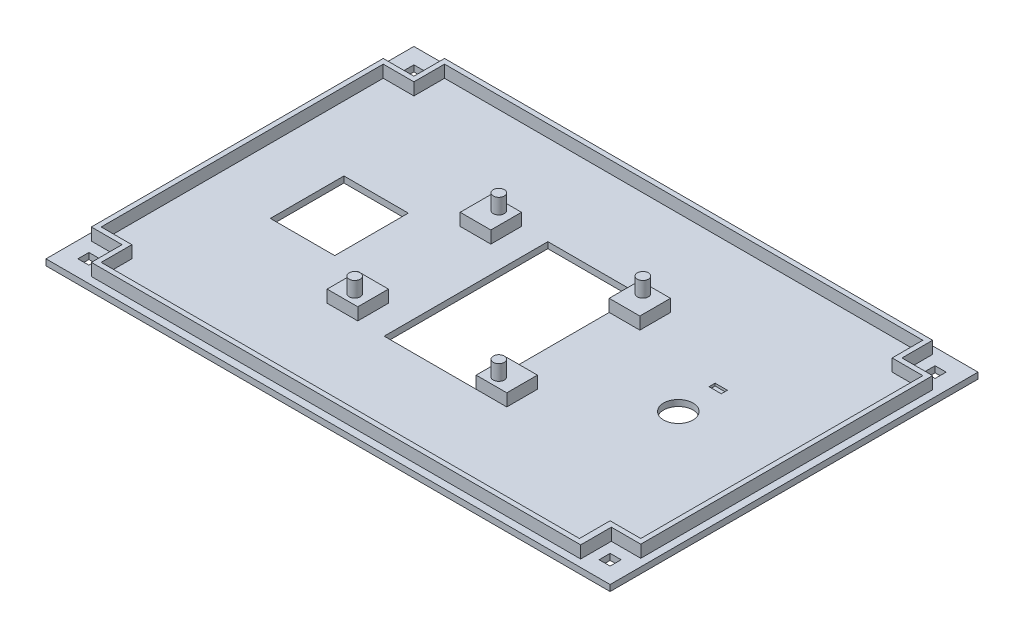
SolidWorks part; units mm, degrees
ref_plane "Спереди" through (0, 0, 0) normal (0, 0, 1) x (1, 0, 0)
ref_plane "Сверху" through (0, 0, 0) normal (0, 1, 0) x (1, 0, 0)
ref_plane "Справа" through (0, 0, 0) normal (1, 0, 0) x (0, 0, -1)
sketch "Эскиз1" plane through (0, 0, 0) normal (0, 1, 0) x (1, 0, 0)
  line L0 (0, 0) -> (92, 0)
  line L1 (0, 0) -> (0, 60)
  line L2 (0, 60) -> (92, 60)
  line L3 (92, 0) -> (92, 60)
  dimension "D1" = 60
  dimension "D2" = 92
extrude "Бобышка-Вытянуть1" add sketch "Эскиз1" along normal blind 1
sketch "Эскиз2" plane through (0, 1, 0) normal (0, 1, 0) x (1, 0, 0)
  line L0 (0, 60) -> (0, 0) construction
  line L1 (91, 1) -> (1, 1)
  line L2 (91, 1) -> (91, 59)
  line L3 (91, 59) -> (1, 59)
  line L4 (1, 1) -> (1, 59)
  line L5 (92, 60) -> (0, 60) construction
  line L6 (92, 0) -> (92, 60) construction
  line L7 (0, 0) -> (92, 0) construction
  line L8 (3.5, 4.4) -> (3.5, 2.6) construction
  line L9 (1, 59) -> (6, 59)
  line L10 (1, 59) -> (1, 54)
  line L11 (1, 54) -> (6, 54)
  line L12 (6, 59) -> (6, 54)
  line L13 (91, 59) -> (86, 59)
  line L14 (91, 59) -> (91, 54)
  line L15 (91, 54) -> (86, 54)
  line L16 (86, 59) -> (86, 54)
  line L17 (91, 1) -> (86, 1)
  line L18 (91, 1) -> (91, 6)
  line L19 (91, 6) -> (86, 6)
  line L20 (86, 1) -> (86, 6)
  line L21 (1, 1) -> (6, 1)
  line L22 (1, 1) -> (1, 6)
  line L23 (1, 6) -> (6, 6)
  line L24 (6, 1) -> (6, 6)
  line L25 (2.6, 57.4) -> (4.4, 57.4)
  line L26 (2.6, 57.4) -> (2.6, 55.6)
  line L27 (2.6, 55.6) -> (4.4, 55.6)
  line L28 (4.4, 57.4) -> (4.4, 55.6)
  line L29 (87.6, 57.4) -> (89.4, 57.4)
  line L30 (87.6, 57.4) -> (87.6, 55.6)
  line L31 (87.6, 55.6) -> (89.4, 55.6)
  line L32 (89.4, 57.4) -> (89.4, 55.6)
  line L33 (87.6, 4.4) -> (89.4, 4.4)
  line L34 (87.6, 4.4) -> (87.6, 2.6)
  line L35 (87.6, 2.6) -> (89.4, 2.6)
  line L36 (89.4, 4.4) -> (89.4, 2.6)
  line L37 (2.6, 4.4) -> (4.4, 4.4)
  line L38 (2.6, 4.4) -> (2.6, 2.6)
  line L39 (2.6, 2.6) -> (4.4, 2.6)
  line L40 (4.4, 4.4) -> (4.4, 2.6)
  line L41 (2.6, 3.5) -> (4.4, 3.5) construction
  line L42 (3.5, 57.4) -> (3.5, 55.6) construction
  line L43 (2.6, 56.5) -> (4.4, 56.5) construction
  line L44 (88.5, 57.4) -> (88.5, 55.6) construction
  line L45 (87.6, 56.5) -> (89.4, 56.5) construction
  line L46 (88.5, 4.4) -> (88.5, 2.6) construction
  line L47 (87.6, 3.5) -> (89.4, 3.5) construction
  line L48 (3.5, 54) -> (3.5, 59) construction
  line L49 (6, 56.5) -> (1, 56.5) construction
  line L50 (86, 56.5) -> (91, 56.5) construction
  line L51 (88.5, 54) -> (88.5, 59) construction
  line L52 (88.5, 6) -> (88.5, 1) construction
  line L53 (86, 3.5) -> (91, 3.5) construction
  line L54 (3.5, 6) -> (3.5, 1) construction
  line L55 (6, 3.5) -> (1, 3.5) construction
  dimension "D1" = 1
  dimension "D2" = 1
  dimension "D3" = 1
  dimension "D4" = 1
  dimension "D5" = 5
  dimension "D6" = 5
  dimension "D7" = 5
  dimension "D8" = 5
  dimension "D9" = 5
  dimension "D10" = 5
  dimension "D11" = 5
  dimension "D12" = 5
  dimension "D13" = 1.8
  dimension "D14" = 1.8
  dimension "D15" = 1.8
  dimension "D16" = 1.8
  dimension "D17" = 1.8
  dimension "D18" = 1.8
  dimension "D19" = 1.8
  dimension "D20" = 1.8
sketch "Эскиз3" plane through (0, 1, 0) normal (0, 1, 0) x (1, 0, 0)
  line L0 (7, 58) -> (7, 53)
  line L1 (7, 53) -> (2, 53)
  line L2 (2, 53) -> (2, 7)
  line L3 (2, 7) -> (7, 7)
  line L4 (7, 7) -> (7, 2)
  line L5 (7, 2) -> (85, 2)
  line L6 (85, 2) -> (85, 7)
  line L7 (85, 7) -> (90, 7)
  line L8 (90, 7) -> (90, 53)
  line L9 (90, 53) -> (85, 53)
  line L10 (85, 53) -> (85, 58)
  line L11 (85, 58) -> (7, 58)
  line L22 (85.8, 53.8) -> (90.8, 53.8)
  line L23 (90.8, 53.8) -> (90.8, 6.2)
  line L24 (90.8, 6.2) -> (86, 6.2)
  line L25 (86, 6.2) -> (86, 1.2)
  line L26 (86, 1.2) -> (6.2, 1.2)
  line L27 (6.2, 1.2) -> (6.2, 6.2)
  line L28 (6.2, 6.2) -> (1.2, 6.2)
  line L29 (1.2, 6.2) -> (1.2, 53.8)
  line L30 (1.2, 53.8) -> (6.2, 53.8)
  line L31 (6.2, 53.8) -> (6.2, 58.8)
  line L32 (6.2, 58.8) -> (85.8, 58.8)
  line L33 (85.8, 58.8) -> (85.8, 53.8)
  point P8 (0, 0)
  point P13 (0, 0)
  dimension "D1" = 78
  dimension "D2" = 46
  dimension "D3" = 46
  dimension "D4" = 78
  dimension "D5" = 5
  dimension "D6" = 5
  dimension "D7" = 5
  dimension "D8" = 5
  dimension "D9" = 5
  dimension "D10" = 5
  dimension "D11" = 0.8
  dimension "D12" = 0.8
  dimension "D13" = 0.8
  dimension "D14" = 0.8
  dimension "D15" = 0.8
  dimension "D16" = 0.8
  dimension "D17" = 0.8
  dimension "D18" = 0.8
extrude "Бобышка-Вытянуть3" add sketch "Эскиз3" along normal blind 2
sketch "Эскиз6" plane through (0, 1, 0) normal (0, 1, 0) x (1, 0, 0)
  line L1 (2.6, 57.4) -> (4.4, 57.4)
  line L2 (2.6, 57.4) -> (2.6, 55.6)
  line L3 (2.6, 55.6) -> (4.4, 55.6)
  line L4 (4.4, 57.4) -> (4.4, 55.6)
extrude "Вырез-Вытянуть3" cut sketch "Эскиз6" against normal blind 1
sketch "Эскиз7" plane through (0, 1, 0) normal (0, 1, 0) x (1, 0, 0)
  line L1 (87.6, 57.4) -> (89.4, 57.4)
  line L2 (87.6, 57.4) -> (87.6, 55.6)
  line L3 (87.6, 55.6) -> (89.4, 55.6)
  line L4 (89.4, 57.4) -> (89.4, 55.6)
extrude "Вырез-Вытянуть4" cut sketch "Эскиз7" against normal blind 1
sketch "Эскиз8" plane through (0, 1, 0) normal (0, 1, 0) x (1, 0, 0)
  line L1 (87.6, 4.4) -> (89.4, 4.4)
  line L2 (87.6, 4.4) -> (87.6, 2.6)
  line L3 (87.6, 2.6) -> (89.4, 2.6)
  line L4 (89.4, 4.4) -> (89.4, 2.6)
extrude "Вырез-Вытянуть5" cut sketch "Эскиз8" against normal blind 1
sketch "Эскиз9" plane through (0, 1, 0) normal (0, 1, 0) x (1, 0, 0)
  line L1 (2.6, 4.4) -> (4.4, 4.4)
  line L2 (2.6, 4.4) -> (2.6, 2.6)
  line L3 (2.6, 2.6) -> (4.4, 2.6)
  line L4 (4.4, 4.4) -> (4.4, 2.6)
extrude "Вырез-Вытянуть6" cut sketch "Эскиз9" against normal blind 1
sketch "Эскиз10" plane through (0, 1, 0) normal (0, 1, 0) x (1, 0, 0)
  line L0 (12.5878, 30) -> (23.0878, 30) construction
  line L1 (12.5878, 36) -> (23.0878, 36)
  line L2 (12.5878, 36) -> (12.5878, 24)
  line L3 (12.5878, 24) -> (23.0878, 24)
  line L4 (23.0878, 36) -> (23.0878, 24)
  line L5 (2, 30) -> (90, 30) construction
  line L6 (2, 53) -> (2, 7) construction
  line L7 (90, 7) -> (90, 53) construction
  dimension "D1" = 10.5
  dimension "D2" = 12
sketch "Эскиз11" plane through (0, 1, 0) normal (0, 1, 0) x (1, 0, 0)
  line L0 (73.1241, 37) -> (73.1241, 36) construction
  line L1 (72.1241, 37) -> (74.1241, 37)
  line L2 (72.1241, 37) -> (72.1241, 36)
  line L3 (72.1241, 36) -> (74.1241, 36)
  line L4 (74.1241, 37) -> (74.1241, 36)
  line L5 (70.7241, 30) -> (75.5241, 30) construction
  line L6 (2, 30) -> (90, 30) construction
  circle A0 centre (73.1241, 30) radius 2.4
  dimension "D1" = 4.8
  dimension "D2" = 1
  dimension "D3" = 2
  dimension "D4" = 6
sketch "Эскиз14" plane through (0, 1, 0) normal (0, 1, 0) x (1, 0, 0)
  line L0 (46, 58) -> (46, 2) construction
  line L1 (85, 58) -> (7, 58) construction
  line L2 (7, 2) -> (85, 2) construction
  line L3 (90, 7) -> (90, 53) construction
  line L4 (2, 30) -> (90, 30) construction
  line L5 (2, 53) -> (2, 7) construction
sketch "Эскиз15" plane through (0, 1, 0) normal (0, 1, 0) x (1, 0, 0)
  line L0 (2, 30) -> (90, 30) construction
  line L1 (38.5, 43.35) -> (53.5, 43.35)
  line L2 (38.5, 43.35) -> (38.5, 16.65)
  line L3 (38.5, 16.65) -> (53.5, 16.65)
  line L4 (53.5, 43.35) -> (53.5, 16.65)
  line L5 (38.5, 30) -> (53.5, 30) construction
  line L6 (46, 43.35) -> (46, 16.65) construction
  line L7 (46, 58) -> (46, 2) construction
  dimension "D1" = 15
  dimension "D2" = 26.7
extrude "Вырез-Вытянуть8" cut sketch "Эскиз15" against normal blind 1
sketch "Эскиз17" plane through (0, 1, 0) normal (0, 1, 0) x (1, 0, 0)
  line L1 (53.5, 43.35) -> (34.2, 43.35)
  line L2 (53.5, 43.35) -> (53.5, 16.65)
  line L3 (53.5, 16.65) -> (34.2, 16.65)
  line L4 (34.2, 43.35) -> (34.2, 16.65)
  dimension "D1" = 19.3
  dimension "D2" = 26.7
sketch "Эскиз18" plane through (0, 1, 0) normal (0, 1, 0) x (1, 0, 0)
  line L1 (34.2, 43.35) -> (29.2, 43.35)
  line L2 (34.2, 43.35) -> (34.2, 38.35)
  line L3 (34.2, 38.35) -> (29.2, 38.35)
  line L4 (29.2, 43.35) -> (29.2, 38.35)
  line L5 (34.2, 16.65) -> (29.2, 16.65)
  line L6 (34.2, 16.65) -> (34.2, 21.65)
  line L7 (34.2, 21.65) -> (29.2, 21.65)
  line L8 (29.2, 16.65) -> (29.2, 21.65)
  line L9 (53.5, 43.35) -> (58.5, 43.35)
  line L10 (53.5, 43.35) -> (53.5, 38.35)
  line L11 (53.5, 38.35) -> (58.5, 38.35)
  line L12 (58.5, 43.35) -> (58.5, 38.35)
  line L13 (53.5, 16.65) -> (58.5, 16.65)
  line L14 (53.5, 16.65) -> (53.5, 21.65)
  line L15 (53.5, 21.65) -> (58.5, 21.65)
  line L16 (58.5, 16.65) -> (58.5, 21.65)
  dimension "D1" = 5
  dimension "D2" = 5
extrude "Бобышка-Вытянуть4" add sketch "Эскиз18" along normal blind 2
sketch "Эскиз19" plane through (0, 3, 0) normal (0, 1, 0) x (1, 0, 0)
  line L0 (31.2, 18.25) -> (33, 18.25) construction
  line L1 (54.7, 18.25) -> (56.5, 18.25) construction
  line L2 (55.6, 19.15) -> (55.6, 17.35) construction
  line L3 (32.1, 19.15) -> (32.1, 17.35) construction
  line L4 (32.1, 42.65) -> (32.1, 40.85) construction
  line L5 (31.2, 41.75) -> (33, 41.75) construction
  line L6 (55.6, 42.65) -> (55.6, 40.85) construction
  line L7 (54.7, 41.75) -> (56.5, 41.75) construction
  line L8 (2, 30) -> (90, 30) construction
  line L9 (34.2, 38.35) -> (34.2, 43.35) construction
  circle A0 centre (32.1, 41.75) radius 0.9
  circle A1 centre (32.1, 18.25) radius 0.9
  circle A2 centre (55.6, 41.75) radius 0.9
  circle A3 centre (55.6, 18.25) radius 0.9
  dimension "D1" = 1.8
  dimension "D2" = 1.8
  dimension "D3" = 1.8
  dimension "D4" = 1.8
  dimension "D5" = 23.5
  dimension "D6" = 11.75
  dimension "D7" = 23.5
  dimension "D8" = 2.1
extrude "Бобышка-Вытянуть5" add sketch "Эскиз19" along normal blind 2.5
extrude "Вырез-Вытянуть9" cut sketch "Эскиз10" against normal blind 1
sketch "Эскиз20" plane through (0, 1, 0) normal (0, 1, 0) x (1, 0, 0)
  circle A0 centre (73.1241, 30) radius 2.4
extrude "Вырез-Вытянуть11" cut sketch "Эскиз20" against normal blind 1
sketch "Эскиз21" plane through (0, 1, 0) normal (0, 1, 0) x (1, 0, 0)
  line L1 (72.1241, 37) -> (74.1241, 37)
  line L2 (72.1241, 37) -> (72.1241, 36)
  line L3 (72.1241, 36) -> (74.1241, 36)
  line L4 (74.1241, 37) -> (74.1241, 36)
extrude "Вырез-Вытянуть12" cut sketch "Эскиз21" against normal blind 0.4
sketch "Эскиз22" plane through (0, 0, 0) normal (0, -1, 0) x (-1, 0, 0)
  text T0 "СТАРТ" font "Arial" height in points 12
  text T1 "без ALARM" font "Arial" height in points 12
  text T2 "c ALARM" font "Arial" height in points 12
extrude "Вырез-Вытянуть13" cut sketch "Эскиз22" against normal blind 0.4
